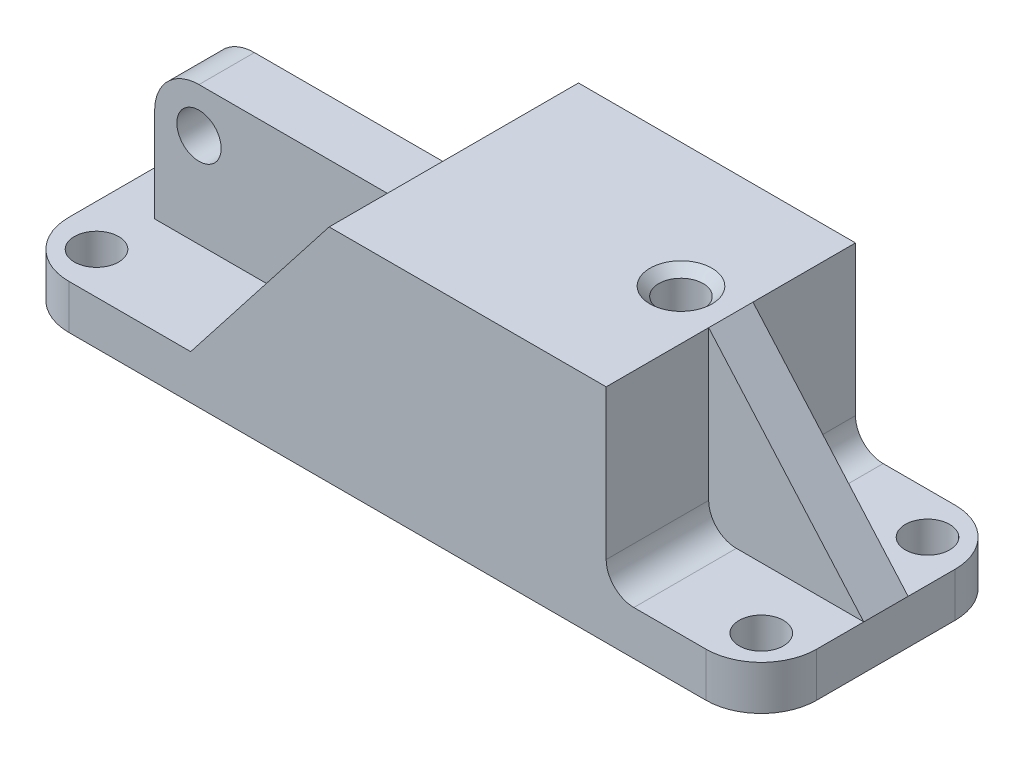
SolidWorks part; units mm, degrees
ref_plane "Спереди(XY)" through (0, 0, 0) normal (0, 0, 1) x (1, 0, 0)
ref_plane "Сверху(XZ)" through (0, 0, 0) normal (0, 1, 0) x (1, 0, 0)
ref_plane "Справа(ZY)" through (0, 0, 0) normal (1, 0, 0) x (0, 0, -1)
sketch "Эскиз1" plane through (0, 0, 0) normal (0, 0, 1) x (1, 0, 0)
  line L0 (0, 0) -> (135, 0)
  line L1 (135, 0) -> (135, 8)
  line L2 (135, 8) -> (107, 8)
  line L3 (107, 8) -> (107, 40)
  line L4 (107, 40) -> (57, 40)
  line L5 (57, 40) -> (32, 8)
  line L6 (32, 8) -> (0, 8)
  line L7 (0, 8) -> (0, 0)
  line L8 (32, 8) -> (32, 44.6545) construction
  dimension "D1" = 135
  dimension "D2" = 50
  dimension "D3" = 28
  dimension "D4" = 25
  dimension "D5" = 40
  dimension "D6" = 8
extrude "Бобышка-Вытянуть1" add sketch "Эскиз1" along normal mid plane 45
sketch "Эскиз2" plane through (0, 0, 0) normal (0, 0, 1) x (1, 0, 0)
  line L0 (8, 8) -> (8, 25)
  line L1 (16, 33) -> (51.5313, 33)
  line L2 (107, 40) -> (135, 8)
  line L3 (135, 8) -> (107, 8)
  line L4 (107, 8) -> (107, 40)
  line L5 (51.5313, 33) -> (32, 8)
  line L6 (32, 8) -> (8, 8)
  line L8 (0, 8) -> (0, 0)
  line L9 (0, 0) -> (135, 0)
  line L10 (135, 0) -> (135, 8)
  line L11 (135, 8) -> (107, 8)
  line L12 (107, 8) -> (107, 40)
  line L13 (107, 40) -> (57, 40)
  line L14 (57, 40) -> (32, 8)
  line L15 (32, 8) -> (0, 8)
  line L16 (0, 8) -> (0, 0) construction
  line L17 (0, 0) -> (135, 0) construction
  line L18 (135, 0) -> (135, 8) construction
  line L19 (135, 8) -> (107, 8) construction
  line L20 (107, 8) -> (107, 40) construction
  line L21 (107, 40) -> (57, 40) construction
  line L22 (57, 40) -> (32, 8) construction
  line L23 (32, 8) -> (0, 8) construction
  arc A0 (16, 33) -> (8, 25) centre (16, 25) ccw
  circle A1 centre (16, 25) radius 4
  dimension "D3" = 16
  dimension "D4" = 8
  dimension "D2" = 25
  dimension "D5" = 16
  dimension "D1" = 0
extrude "Бобышка-Вытянуть2" add sketch "Эскиз2" along normal mid plane 10 contours L1 L5 L6 L0 A0
extrude "Бобышка-Вытянуть3" add sketch "Эскиз2<3>" along normal mid plane 8 contours L2 L3 L4
sketch "Эскиз2<3>" plane through (0, 0, 0) normal (0, 0, 1) x (1, 0, 0) same geometry as "Эскиз2"
extrude "Вырез-Вытянуть1" cut sketch "Эскиз2<4>" against normal blind 8 and the other way blind 23 contours A1
sketch "Эскиз2<4>" plane through (0, 0, 0) normal (0, 0, 1) x (1, 0, 0) same geometry as "Эскиз2"
sketch "Эскиз3" plane through (0, 0, 0) normal (0, 0, 1) x (1, 0, 0)
  line L0 (107, 40) -> (57, 40) construction
  line L1 (57, 40) -> (32, 8) construction
  line L2 (107, 40) -> (57, 40) construction
  line L3 (57, 40) -> (32, 8) construction
  line L5 (35.902, 0) -> (59.3395, 30)
  line L6 (0, 0) -> (135, 0) construction
  line L7 (59.3395, 30) -> (91, 30)
  line L8 (91, 30) -> (91, 0)
  line L9 (107, 8) -> (107, 40) construction
  line L10 (35.902, 0) -> (91, 0)
  dimension "D1" = 10
  dimension "D2" = 8
  dimension "D3" = 16
extrude "Вырез-Вытянуть2" cut sketch "Эскиз3" against normal mid plane 35
fillet "Скругление1" radius 5 2 edges at (107, 8, 13.25) (107, 8, -13.25)
sketch "Эскиз4" plane through (0, 0, 0) normal (0, -1, 0) x (1, 0, 0)
  line L0 (0, 0) -> (135, 0) construction
  line L4 (0, -22.5) -> (135, -22.5)
  line L5 (135, -22.5) -> (135, 22.5)
  line L6 (135, 22.5) -> (0, 22.5)
  line L7 (0, 22.5) -> (0, -22.5)
  line L8 (0, -22.5) -> (135, -22.5) construction
  line L9 (135, -22.5) -> (135, 22.5) construction
  line L10 (135, 22.5) -> (0, 22.5) construction
  line L11 (0, 22.5) -> (0, -22.5) construction
  circle A0 centre (7.5, 15) radius 7.5 construction
  circle A1 centre (7.5, 15) radius 4
  circle A2 centre (7.5, -15) radius 7.5 construction
  circle A3 centre (7.5, -15) radius 4
  circle A4 centre (127.5, -15) radius 4
  circle A5 centre (127.5, 15) radius 4
  dimension "D2" = 30
  dimension "D3" = 8
  dimension "D4" = 120
  dimension "D1" = 0
extrude "Вырез-Вытянуть4" cut sketch "Эскиз4" against normal blind 35
sketch "Эскиз5" plane through (0, 40, 0) normal (0, 1, 0) x (1, 0, 0)
  line L0 (57, 0) -> (107, 0) construction
  line L6 (107, 22.5) -> (57, 22.5)
  line L7 (57, 22.5) -> (57, -22.5)
  line L8 (57, -22.5) -> (107, -22.5)
  line L9 (107, -22.5) -> (107, -4)
  line L10 (107, -4) -> (107, 4)
  line L11 (107, 4) -> (107, 22.5)
  line L12 (107, 22.5) -> (57, 22.5) construction
  line L13 (57, 22.5) -> (57, -22.5) construction
  line L14 (57, -22.5) -> (107, -22.5) construction
  line L15 (107, -22.5) -> (107, -4) construction
  line L16 (107, -4) -> (107, 4) construction
  line L17 (107, 4) -> (107, 22.5) construction
  circle A0 centre (98, 0) radius 4
  dimension "D2" = 8
  dimension "D3" = 9
  dimension "D1" = 0
extrude "Вырез-Вытянуть5" cut sketch "Эскиз5" against normal blind 47
fillet "Скругление2" radius 10 4 edges at (135, 4, -22.5) (135, 4, 22.5) (0, 4, -22.5) (0, 4, 22.5)
fillet "Скругление3" radius 1 10 edges at (41.7656, 20.5, -5) (41.7656, 20.5, 5) (91, 15, 17.5) (47.6207, 15, 17.5) (75.1697, 30, 17.5) (59.3395, 30, 0) (91, 30, 0) (91, 15, -17.5) (47.6207, 15, -17.5) (75.1697, 30, -17.5)
chamfer "Фаска1" distance 1.6 angle 45 1 edges at (94, 40, 0)
